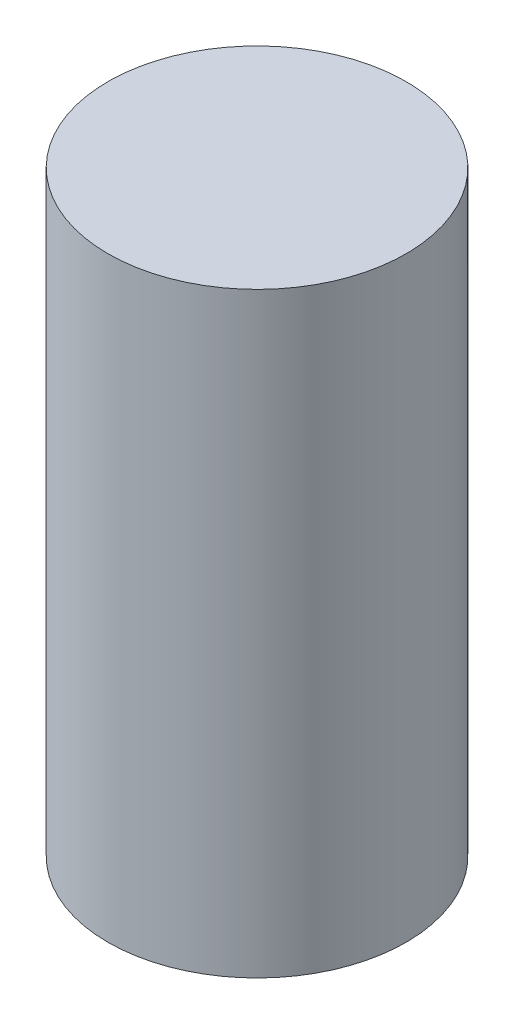
SolidWorks part; units mm, degrees
ref_plane "Front Plane" through (0, 0, 0) normal (0, 0, 1) x (1, 0, 0)
ref_plane "Top Plane" through (0, 0, 0) normal (0, 1, 0) x (1, 0, 0)
ref_plane "Right Plane" through (0, 0, 0) normal (1, 0, 0) x (0, 0, -1)
sketch "Sketch1" plane through (0, 0, 0) normal (0, 1, 0) x (1, 0, 0)
  circle A0 centre (0, 0) radius 5
  dimension "D1" = 10
extrude "Boss-Extrude1" add sketch "Sketch1" along normal mid plane 20
ref_axis "Axis1" through (0, 10, 0) along (0, -1, 0)
